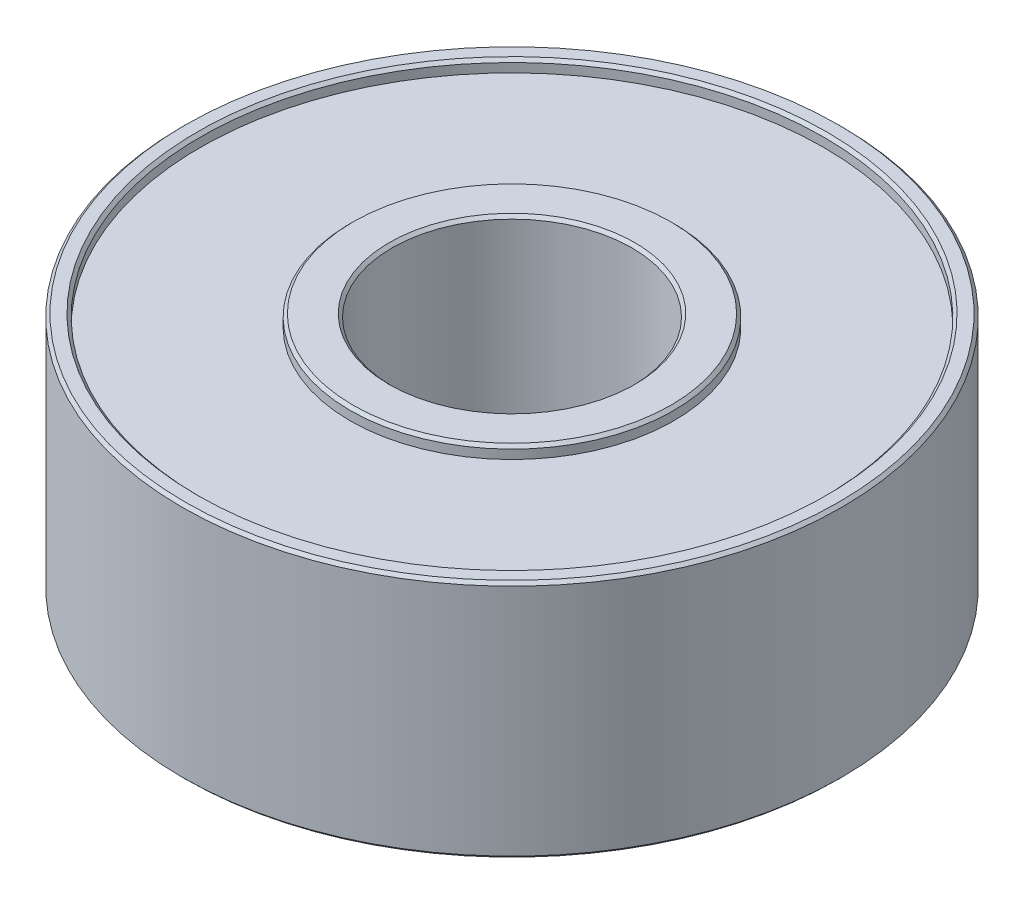
SolidWorks part; units mm, degrees
ref_plane "Спереди" through (0, 0, 0) normal (0, 0, 1) x (1, 0, 0)
ref_plane "Сверху" through (0, 0, 0) normal (0, 1, 0) x (1, 0, 0)
ref_plane "Справа" through (0, 0, 0) normal (1, 0, 0) x (0, 0, -1)
sketch "Эскиз1" plane through (0, 0, 0) normal (0, 1, 0) x (1, 0, 0)
  circle A0 centre (0, 0) radius 5.5
  circle A1 centre (0, 0) radius 2
  dimension "D1" = 11
  dimension "D2" = 4
extrude "Бобышка-Вытянуть1" add sketch "Эскиз1" along normal blind 4
sketch "Эскиз2" plane through (0, 4, 0) normal (0, 1, 0) x (1, 0, 0)
  circle A0 centre (0, 0) radius 2.7
  circle A1 centre (0, 0) radius 5.2
  dimension "D1" = 10.4
  dimension "D2" = 5.4
extrude "Вырез-Вытянуть1" cut sketch "Эскиз2" against normal blind 0.2
extrude "Вырез-Вытянуть2" cut sketch "Эскиз2<2>" against normal through all from offset 3.8 offset against normal yes
sketch "Эскиз2<2>" plane through (0, 4, 0) normal (0, 1, 0) x (1, 0, 0) same geometry as "Эскиз2"
chamfer "Фаска1" distance 0.05 angle 45 8 edges at (0, 0, 2.7) (0, 0, 2) (0, 0, 5.5) (0, 0, 5.2) (0, 4, 2.7) (0, 4, 2) (0, 4, 5.5) (0, 4, 5.2)
